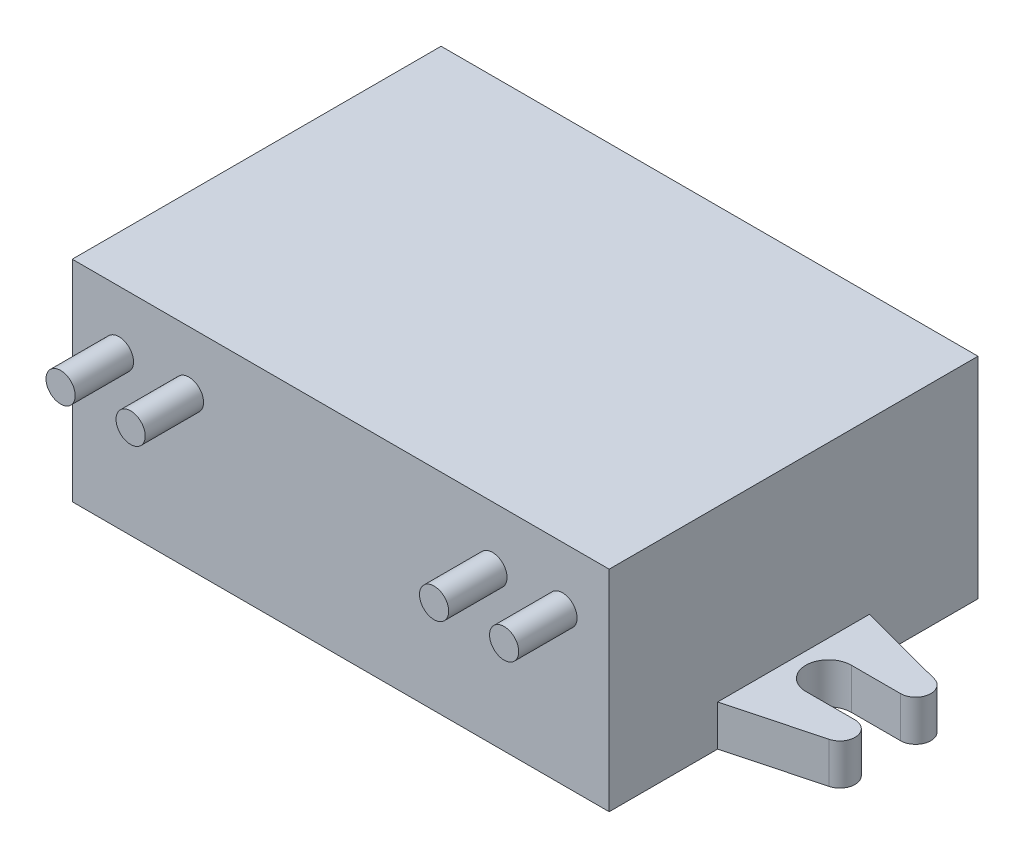
SolidWorks part; units mm, degrees
ref_plane "Front Plane" through (0, 0, 0) normal (0, 0, 1) x (1, 0, 0)
ref_plane "Top Plane" through (0, 0, 0) normal (0, 1, 0) x (1, 0, 0)
ref_plane "Right Plane" through (0, 0, 0) normal (1, 0, 0) x (0, 0, -1)
ref_axis "X" through (-88.99, 0, 0) along (1, 0, 0)
ref_axis "Y" through (0, 55, 0) along (0, -1, 0)
ref_axis "Z" through (0, 0, -88.99) along (0, 0, 1)
sketch "Sketch1" plane through (0, 0, 0) normal (0, 1, 0) x (1, 0, 0)
  line L0 (23, 6.5) -> (30.5464, 4.5)
  line L1 (-23, 15.8) -> (23, 15.8)
  line L2 (-23, 15.8) -> (-23, -15.8)
  line L3 (-23, -15.8) -> (23, -15.8)
  line L4 (23, 15.8) -> (23, -15.8)
  line L5 (-23, 15.8) -> (23, -15.8) construction
  line L6 (-23, -15.8) -> (23, 15.8) construction
  line L7 (30.2142, 1.95) -> (26, 1.95)
  line L8 (26, -1.95) -> (30.2142, -1.95)
  line L9 (30.5464, -4.5) -> (23, -6.5)
  line L10 (0, 0) -> (26, 0) construction
  line L11 (0, 15.8) -> (0, -15.8) construction
  line L12 (-30.5464, -4.5) -> (-23, -6.5)
  line L13 (-26, -1.95) -> (-30.2142, -1.95)
  line L14 (-30.2142, 1.95) -> (-26, 1.95)
  line L15 (-23, 6.5) -> (-30.5464, 4.5)
  arc A0 (30.5464, 4.5) -> (30.2142, 1.95) centre (30.2142, 3.2466) cw
  arc A1 (26, 1.95) -> (26, -1.95) centre (26, 0) ccw
  arc A2 (30.2142, -1.95) -> (30.5464, -4.5) centre (30.2142, -3.2466) cw
  arc A3 (-30.2142, -1.95) -> (-30.5464, -4.5) centre (-30.2142, -3.2466) ccw
  arc A4 (-26, 1.95) -> (-26, -1.95) centre (-26, 0) cw
  arc A5 (-30.5464, 4.5) -> (-30.2142, 1.95) centre (-30.2142, 3.2466) ccw
  point P0 (0, 0)
  point P19 (31.5, 3.0791)
  dimension "D3" = 1.95
  dimension "D4" = 8.5
  dimension "D7" = 3
  dimension "D1" = 31.6
  dimension "D2" = 46
  dimension "D5" = 9
  dimension "D6" = 13
extrude "Boss-Extrude1" add sketch "Sketch1" along normal blind 18 contours L4 L1 L2 L3 region at (0, 0, 0)
extrude "Boss-Extrude2" add sketch "Sketch1<3>" along normal blind 3.5 contours L15 A5 L14 A4 L13 A3 L12 L2 | A2 L8 A1 L7 A0 L0 L4 L9 region at (26.7334, 0, -5.3498) region at (-23.1554, 0, 0)
sketch "Sketch1<3>" plane through (0, 0, 0) normal (0, 1, 0) x (1, 0, 0) same geometry as "Sketch1"
sketch "Sketch2" plane through (0, 0, 15.8) normal (0, 0, 1) x (1, 0, 0)
  line L0 (13, 13) -> (19, 13) construction
  line L1 (19, 13) -> (23, 13) construction
  line L2 (23, 18) -> (23, 0) construction
  line L3 (-23, 18) -> (23, 18) construction
  line L4 (0, 0) -> (0, 18) construction
  line L5 (-23, 0) -> (23, 0) construction
  circle A0 centre (19, 13) radius 1.25
  circle A1 centre (13, 13) radius 1.25
  circle A2 centre (-19, 13) radius 1.25
  circle A3 centre (-13, 13) radius 1.25
  dimension "D1" = 4
  dimension "D3" = 2.5
  dimension "D2" = 6
  dimension "D4" = 5
extrude "Boss-Extrude3" add sketch "Sketch2" along normal blind 5
